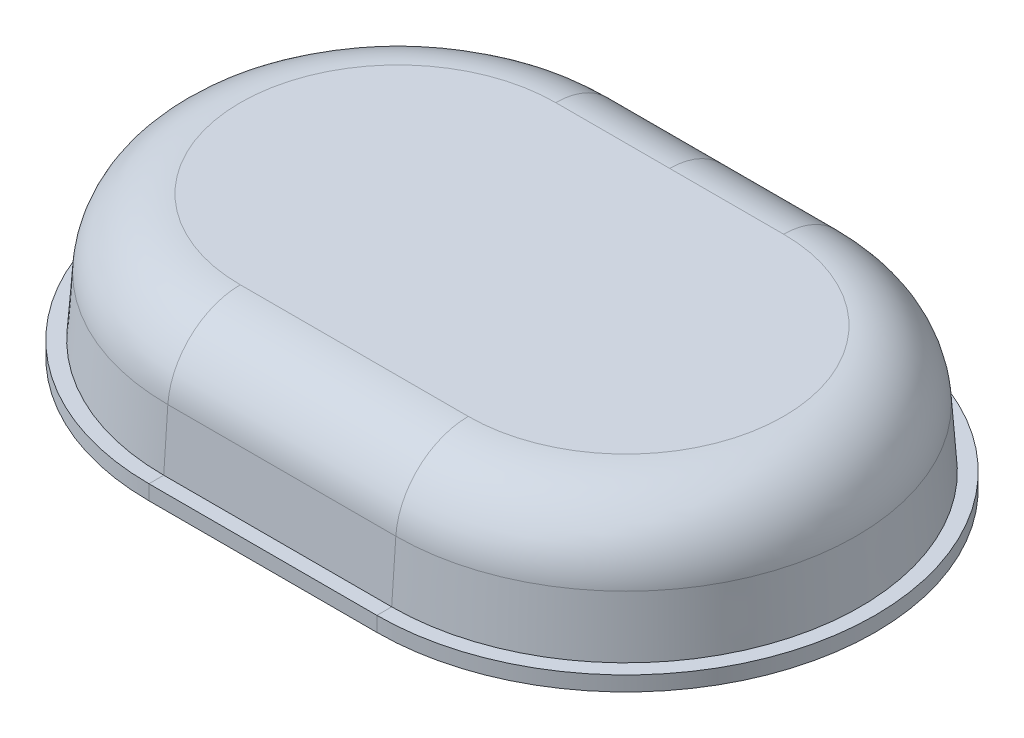
SolidWorks part; units mm, degrees
other "Camera1"
ref_plane "Front Plane" through (0, 0, 0) normal (0, 0, 1) x (1, 0, 0)
ref_plane "Top Plane" through (0, 0, 0) normal (0, 1, 0) x (1, 0, 0)
ref_plane "Right Plane" through (0, 0, 0) normal (1, 0, 0) x (0, 0, -1)
sketch "Sketch1" plane through (0, 0, 0) normal (0, 1, 0) x (1, 0, 0)
  line L0 (-86.997, 0) -> (95.8276, 0) construction
  line L1 (0, 66.4742) -> (0, -65.0025) construction
  line L2 (-27, 55.5) -> (27, 55.5)
  line L3 (-27, -55.5) -> (27, -55.5)
  arc A0 (-27, 55.5) -> (-27, -55.5) centre (-27, 0) ccw
  arc A1 (27, 55.5) -> (27, -55.5) centre (27, 0) cw
  point P6 (-82.5, 0)
  dimension "D2" = 55.5
  dimension "D1" = 82.5
extrude "Boss-Extrude1" add sketch "Sketch1" along normal blind 3.5
sketch "Sketch6" plane through (0, 3.5, 0) normal (0, 1, 0) x (1, 0, 0)
  line L2 (-27, -55.5) -> (27, -55.5)
  line L3 (27, 55.5) -> (-27, 55.5)
  line L4 (-27, -55.5) -> (27, -55.5)
  line L5 (27, 55.5) -> (-27, 55.5)
  arc A2 (-27, 55.5) -> (-27, -55.5) centre (-27, 0) ccw
  arc A3 (27, -55.5) -> (27, 55.5) centre (27, 0) ccw
  arc A4 (-27, 55.5) -> (-27, -55.5) centre (-27, 0) ccw
  arc A5 (27, -55.5) -> (27, 55.5) centre (27, 0) ccw
  dimension "D1" = 0
extrude "Boss-Extrude2" add sketch "Sketch6" along normal blind 30 draft 4
sketch "Sketch7" plane through (0, 0, 0) normal (1, 0, 0) x (0, 0, -1)
  line L0 (55.5, 3.5) -> (55.5, 45.8936) construction
  line L1 (-55.5, 3.5) -> (-55.5, 48.5755) construction
  line L2 (54.521, 17.5) -> (-54.521, 17.5) construction
  line L3 (55.5, 3.5) -> (-55.5, 3.5) construction
  line L4 (53.4022, 33.5) -> (55.5, 3.5) construction
  line L5 (-53.4022, 33.5) -> (-55.5, 3.5) construction
  line L6 (53.4022, 33.5) -> (-53.4022, 33.5) construction
  line L7 (37.3631, 33.5) -> (37.3631, 41.3169)
  line L8 (37.3631, 41.3169) -> (63.9734, 41.3169)
  line L9 (63.9734, 41.3169) -> (63.9734, 17.5)
  line L10 (63.9734, 17.5) -> (54.521, 17.5)
  line L11 (63.9734, 41.3169) -> (53.4022, 33.5) construction
  arc A0 (54.521, 17.5) -> (37.3631, 33.5) centre (37.3631, 16.3002) ccw
  dimension "D1" = 14
  dimension "D2" = 109.042
  dimension "D3" = 26.6103
  dimension "D4" = 23.8169
sketch "Sketch8" plane through (0, 33.5, 0) normal (0, 1, 0) x (1, 0, 0)
  line L2 (-27, -53.4022) -> (27, -53.4022)
  line L3 (27, 53.4022) -> (-27, 53.4022)
  line L4 (-27, -53.4022) -> (27, -53.4022)
  line L5 (27, 53.4022) -> (-27, 53.4022)
  arc A2 (-27, 53.4022) -> (-27, -53.4022) centre (-27, 0) ccw
  arc A3 (27, -53.4022) -> (27, 53.4022) centre (27, 0) ccw
  arc A4 (-27, 53.4022) -> (-27, -53.4022) centre (-27, 0) ccw
  arc A5 (27, -53.4022) -> (27, 53.4022) centre (27, 0) ccw
  dimension "D1" = 0
sweep "Cut-Sweep5" cut profiles "Sketch7" path "Sketch8"
shell "Shell1" thickness 1.5 removed face at (0, 0, 0)
sketch "Sketch9" plane through (0, 0, 0) normal (1, 0, 0) x (0, 0, -1)
  line L0 (55.5, 3.5) -> (59, 3.5)
  line L1 (59, 3.5) -> (59, 0)
  line L2 (59, 0) -> (55.5, 0)
  line L3 (55.5, 0) -> (55.5, 3.5)
  dimension "D1" = 3.5
sketch "Sketch10" plane through (0, 0, 0) normal (0, -1, 0) x (1, 0, 0)
  line L0 (27, -55.5) -> (-27, -55.5) construction
  line L1 (-27, 55.5) -> (27, 55.5) construction
  line L2 (27, -55.5) -> (-27, -55.5)
  line L3 (-27, 55.5) -> (27, 55.5)
  arc A0 (-27, 55.5) -> (-27, -55.5) centre (-27, 0) ccw construction
  arc A1 (27, -55.5) -> (27, 55.5) centre (27, 0) ccw construction
  arc A2 (-27, 55.5) -> (-27, -55.5) centre (-27, 0) ccw
  arc A3 (27, -55.5) -> (27, 55.5) centre (27, 0) ccw
sweep "Sweep1" add profiles "Sketch9" path "Sketch10"
